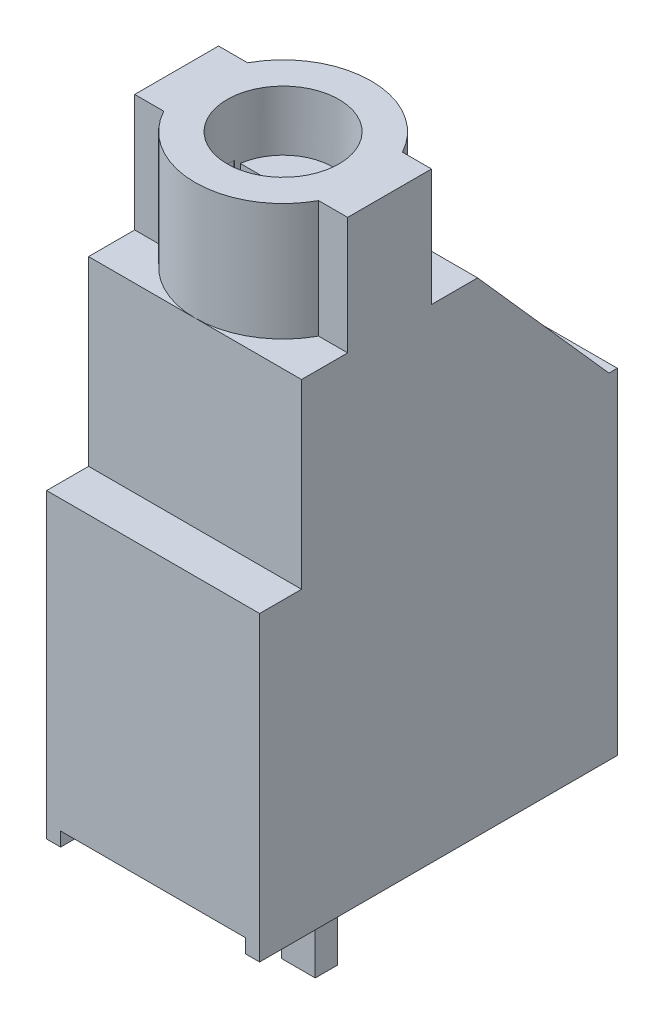
SolidWorks part; units mm, degrees
material "ABS"
ref_plane "前视基准面" through (0, 0, 0) normal (0, 0, 1) x (1, 0, 0)
ref_plane "上视基准面" through (0, 0, 0) normal (0, 1, 0) x (1, 0, 0)
ref_plane "右视基准面" through (0, 0, 0) normal (1, 0, 0) x (0, 0, -1)
sketch "草图2" plane through (0, 0, 0) normal (1, 0, 0) x (0, 0, -1)
  line L0 (6.4, 0) -> (-6.4, 0)
  line L1 (-6.4, 0) -> (-6.4, 10.8)
  line L2 (-6.4, 10.8) -> (-4.9, 10.8)
  line L3 (-4.9, 10.8) -> (-4.9, 17.3)
  line L4 (-4.9, 17.3) -> (-3.25, 17.3)
  line L5 (-3.25, 17.3) -> (-3.25, 21.5)
  line L6 (-3.25, 21.5) -> (-0.25, 21.5)
  line L7 (-0.25, 21.5) -> (-0.25, 17.3)
  line L8 (6.1, 12) -> (1.4, 17.3)
  line L9 (6.1, 12) -> (6.4, 12)
  line L10 (6.4, 12) -> (6.4, 0)
  line L11 (0, 82.2465) -> (0, -29.6489) construction
  line L12 (1.4, 17.3) -> (-0.25, 17.3)
  line L13 (-1.75, 24.1268) -> (-1.75, 14.5128) construction
  dimension "D1" = 12.8
  dimension "D2" = 21.5
  dimension "D3" = 3
  dimension "D4" = 1.5
  dimension "D5" = 4.2
  dimension "D6" = 10.8
  dimension "D7" = 12
  dimension "D8" = 6.3
  dimension "D9" = 0.3
extrude "凸台-拉伸1" add sketch "草图2" along normal blind 3.81 and the other way blind 3.81
sketch "草图3" plane through (0, 21.5, 0) normal (0, 1, 0) x (1, 0, 0)
  line L0 (-8.5326, -1.75) -> (7.6987, -1.75) construction
  line L1 (-3.81, 1.4) -> (3.81, 1.4) construction
  line L2 (-3.81, -4.9) -> (3.81, -4.9) construction
  line L3 (0, 8.5645) -> (0, -8.8898) construction
  line L4 (-3.81, -4.9) -> (3.81, -4.9) construction
  circle A0 centre (0, -1.75) radius 3.15
extrude "凸台-拉伸2" add sketch "草图3" against normal up to next (21.5 mm away)
sketch "草图4" plane through (0, 21.5, 0) normal (0, 1, 0) x (1, 0, 0)
  circle A0 centre (0, -1.75) radius 2
  arc A1 (2.7699, -0.25) -> (0, 1.4) centre (0, -1.75) ccw construction
  dimension "D1" = 4
extrude "切除-拉伸1" cut sketch "草图4" against normal blind 2
sketch "草图7" plane through (0, 19.5, 0) normal (0, 1, 0) x (1, 0, 0)
  circle A1 centre (0, -1.75) radius 2 construction
  circle A2 centre (0, -1.75) radius 2
  circle A3 centre (0, -1.75) radius 1.8
  dimension "D1" = 0.2
extrude "切除-拉伸5" cut sketch "草图7" against normal blind 0.5
sketch "草图5" plane through (0, 19.5, 0) normal (0, 1, 0) x (1, 0, 0)
  line L0 (2.9198, -1.75) -> (-3.0795, -1.75) construction
  line L1 (-2, -1.5) -> (2, -1.5)
  line L2 (-2, -1.5) -> (-2, -2)
  line L3 (-2, -2) -> (2, -2)
  line L4 (2, -1.5) -> (2, -2)
  line L5 (0, 1.1079) -> (0, -1.2643) construction
  line L10 (-3.81, 1.4) -> (0, 1.4) construction
  line L11 (-3.81, -4.9) -> (3.81, -4.9) construction
  circle A0 centre (0, -1.75) radius 2 construction
  dimension "D1" = 0.5
extrude "切除-拉伸2" cut sketch "草图5" against normal blind 0.5
sketch "草图8" plane through (0, 0, -6.4) normal (0, 0, -1) x (-1, 0, 0)
  line L0 (0, -8.4917) -> (0, 27.7719) construction
  line L1 (3.81, 0) -> (-3.81, 0) construction
  line L2 (-1.75, 9) -> (1.75, 9)
  line L3 (-1.75, 9) -> (-1.75, 4.5)
  line L4 (-1.75, 4.5) -> (1.75, 4.5)
  line L5 (1.75, 9) -> (1.75, 4.5)
  dimension "D1" = 4.5
  dimension "D2" = 3.5
  dimension "D3" = 4.5
extrude "切除-拉伸6" cut sketch "草图8" against normal blind 2
chamfer "倒角1" distance 1 angle 60 4 edges at (0, 9, -6.4) (-1.75, 6.75, -6.4) (1.75, 6.75, -6.4) (0, 4.5, -6.4) first distance on face at (0, 6.75, -6.4)
sketch "草图9" plane through (0, 0, 0) normal (0, -1, 0) x (1, 0, 0)
  line L0 (-3.81, 6.4) -> (3.81, 6.4) construction
  line L1 (-3.31, 6.4) -> (3.31, 6.4)
  line L2 (-3.31, 6.4) -> (-3.31, -6.4)
  line L3 (-3.31, -6.4) -> (3.31, -6.4)
  line L4 (3.31, 6.4) -> (3.31, -6.4)
  line L5 (-3.81, -6.4) -> (3.81, -6.4) construction
  line L6 (0, 11.6522) -> (0, -12.157) construction
  line L7 (-3.81, 6.4) -> (-3.81, -6.4) construction
  line L8 (3.81, 6.4) -> (3.81, -6.4) construction
  point P10 (-3.81, 0)
  dimension "D1" = 0.5
  dimension "D2" = 0.5
extrude "切除-拉伸7" cut sketch "草图9" against normal blind 0.5
sketch "草图10" plane through (0, 0.5, 0) normal (0, -1, 0) x (1, 0, 0)
  line L0 (0, 2.8369) -> (0, -1.126) construction
  line L1 (-0.6, 1.2) -> (0.6, 1.2)
  line L2 (-0.6, 1.2) -> (-0.6, 0.4)
  line L3 (-0.6, 0.4) -> (0.6, 0.4)
  line L4 (0.6, 1.2) -> (0.6, 0.4)
  line L5 (-1.1133, 0.8) -> (0.9224, 0.8) construction
  line L6 (3.31, 6.4) -> (-3.31, 6.4) construction
  dimension "D1" = 1.2
  dimension "D2" = 0.8
  dimension "D3" = 5.6
extrude "凸台-拉伸4" add sketch "草图10" along normal blind 5.2
